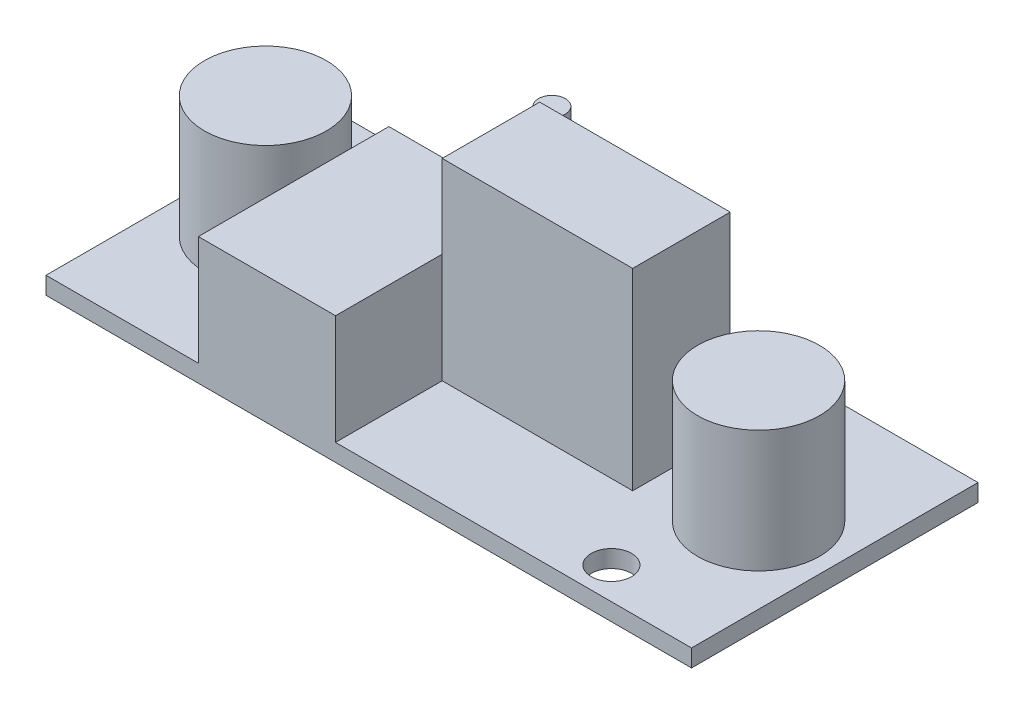
SolidWorks part; units mm, degrees
ref_plane "Front Plane" through (0, 0, 0) normal (0, 0, 1) x (1, 0, 0)
ref_plane "Top Plane" through (0, 0, 0) normal (0, 1, 0) x (1, 0, 0)
ref_plane "Right Plane" through (0, 0, 0) normal (1, 0, 0) x (0, 0, -1)
sketch "Sketch1" plane through (0, 0, 0) normal (0, 1, 0) x (1, 0, 0)
  line L1 (-26.8986, -11.938) -> (26.8986, -11.938)
  line L2 (-26.8986, -11.938) -> (-26.8986, 11.938)
  line L3 (-26.8986, 11.938) -> (26.8986, 11.938)
  line L4 (26.8986, -11.938) -> (26.8986, 11.938)
  line L5 (-26.8986, -11.938) -> (26.8986, 11.938) construction
  line L6 (-26.8986, 11.938) -> (26.8986, -11.938) construction
  point P0 (0, 0)
extrude "Boss-Extrude1" add sketch "Sketch1" along normal blind 1.4478 contours L2 L1 L4 L3
sketch "Sketch2" plane through (0, 1.4478, 0) normal (0, 1, 0) x (1, 0, 0)
  line L0 (26.8986, -11.938) -> (17.5768, -11.938)
  line L1 (-26.8986, -11.938) -> (26.8986, -11.938) construction
  circle A0 centre (17.5768, -9.29) radius 1.6827
  circle A3 centre (-17.5768, 9.2901) radius 1.6827
extrude "Cut-Extrude1" cut sketch "Sketch2" against normal through all contours A3 | A0
sketch "Sketch3" plane through (0, 1.4478, 0) normal (0, 1, 0) x (1, 0, 0)
  circle A0 centre (-20.5486, 0) radius 5.08
  circle A1 centre (20.5486, 0) radius 5.08
extrude "Boss-Extrude2" add sketch "Sketch3" along normal blind 10.16 contours A1 | A0 | A0 region at (-20.5486, 1.4478, 0) region at (20.5486, 1.4478, 0)
sketch "Sketch4" plane through (0, 1.4478, 0) normal (0, 1, 0) x (1, 0, 0)
  line L0 (-26.8986, -11.938) -> (-14.1986, -11.938)
  line L1 (-26.8986, -11.938) -> (26.8986, -11.938) construction
  line L3 (-14.1986, -11.938) -> (-2.7686, -11.938)
  line L4 (-14.1986, -11.938) -> (-14.1986, 3.937)
  line L5 (-14.1986, 3.937) -> (-2.7686, 3.937)
  line L6 (-2.7686, -11.938) -> (-2.7686, 3.937)
extrude "Boss-Extrude3" add sketch "Sketch4" along normal blind 9.144 contours L4 L3 L6 L5
sketch "Sketch5" plane through (0, 1.4478, 0) normal (0, 1, 0) x (1, 0, 0)
  line L0 (-26.8986, 11.938) -> (-8.6106, 11.938)
  line L1 (-26.8986, 11.938) -> (26.8986, 11.938) construction
  line L3 (-8.6106, 11.938) -> (0.8636, 11.938)
  line L4 (-8.6106, 11.938) -> (-8.6106, 7.7216)
  line L5 (-8.6106, 7.7216) -> (0.8636, 7.7216)
  line L6 (0.8636, 11.938) -> (0.8636, 7.7216)
extrude "Boss-Extrude4" add sketch "Sketch5" along normal blind 9.144 contours L4 L3 L6 L5
sketch "Sketch6" plane through (0, 10.5918, 0) normal (0, 1, 0) x (1, 0, 0)
  circle A0 centre (-7.3406, 10.668) radius 1.1176
extrude "Boss-Extrude5" add sketch "Sketch6" along normal blind 1.524 contours A0
sketch "Sketch7" plane through (0, 1.4478, 0) normal (0, 1, 0) x (1, 0, 0)
  line L0 (-2.7686, -11.938) -> (-2.7686, -3.048)
  line L1 (-2.7686, -11.938) -> (-2.7686, 3.937) construction
  line L3 (-2.7686, -3.048) -> (13.1064, -3.048)
  line L4 (-2.7686, -3.048) -> (-2.7686, 5.08)
  line L5 (-2.7686, 5.08) -> (13.1064, 5.08)
  line L6 (13.1064, -3.048) -> (13.1064, 5.08)
extrude "Boss-Extrude6" add sketch "Sketch7" along normal blind 16.0528 contours L4 L3 L6 L5
